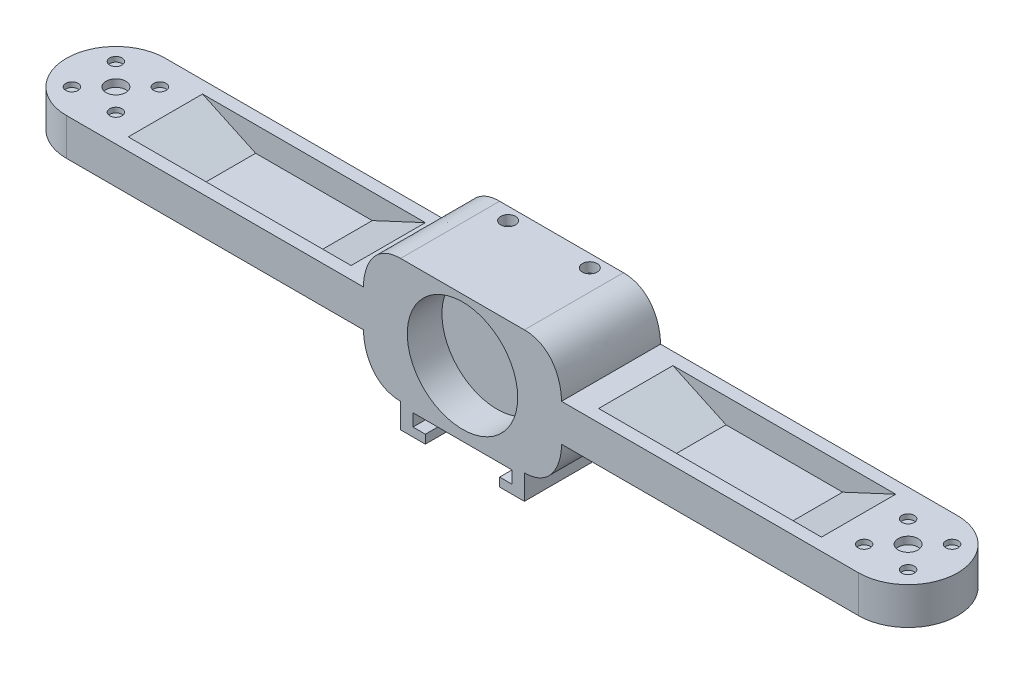
SolidWorks part; units mm, degrees
ref_plane "Front Plane" through (0, 0, 0) normal (0, 0, 1) x (1, 0, 0)
ref_plane "Top Plane" through (0, 0, 0) normal (0, 1, 0) x (1, 0, 0)
ref_plane "Right Plane" through (0, 0, 0) normal (1, 0, 0) x (0, 0, -1)
sketch "Sketch1" plane through (0, 0, 0) normal (0, 1, 0) x (1, 0, 0)
  line L0 (-80, 0) -> (80, 0) construction
  line L1 (-80, 10) -> (80, 10)
  line L2 (-80, -10) -> (80, -10)
  arc A0 (-80, 10) -> (-80, -10) centre (-80, 0) ccw
  arc A1 (80, -10) -> (80, 10) centre (80, 0) ccw
  point P2 (0, 0)
  dimension "D1" = 160
  dimension "D2" = 20
extrude "Boss-Extrude1" add sketch "Sketch1" along normal blind 25 contours L1 A1 L2 A0
sketch "Sketch2" plane through (0, 0, 10) normal (0, 0, 1) x (1, 0, 0)
  line L0 (0, 0) -> (0, 12.5) construction
  circle A0 centre (0, 12.5) radius 11.15
  dimension "D2" = 22.3
  dimension "D1" = 12.5
extrude "Cut-Extrude1" cut sketch "Sketch2" against normal blind 7 contours A0
sketch "Sketch3" plane through (0, 25, 0) normal (0, 1, 0) x (1, 0, 0)
  line L0 (0, 0) -> (20, 0) construction
  line L1 (0, 0) -> (-20, 0) construction
  line L2 (-20, 10) -> (-20, -10)
  line L3 (-80, 10) -> (80, 10) construction
  line L4 (-80, -10) -> (80, -10) construction
  line L5 (20, 10) -> (20, -10)
  line L6 (20, -10) -> (80, -10)
  line L7 (20, 10) -> (80, 10)
  line L8 (-20, 10) -> (-80, 10)
  line L9 (-20, -10) -> (-80, -10)
  arc A0 (-80, 10) -> (-80, -10) centre (-80, 0) ccw
  arc A1 (80, 10) -> (80, -10) centre (80, 0) cw
  dimension "D2" = 20
  dimension "D1" = 20
extrude "Cut-Extrude2" cut sketch "Sketch3" against normal blind 8.75
sketch "Sketch4" plane through (0, 0, 0) normal (0, -1, 0) x (1, 0, 0)
  line L2 (20, 10) -> (20, -10)
  line L3 (-80, 10) -> (80, 10) construction
  line L4 (20, -10) -> (80, -10)
  line L5 (20, 10) -> (80, 10)
  line L6 (-20, 10) -> (-20, -10)
  line L7 (-20, -10) -> (-80, -10)
  line L8 (-20, 10) -> (-80, 10)
  arc A0 (80, 10) -> (80, -10) centre (80, 0) cw
  arc A1 (-80, 10) -> (-80, -10) centre (-80, 0) ccw
extrude "Cut-Extrude3" cut sketch "Sketch4" against normal blind 8.75
sketch "Sketch5" plane through (0, 0, -10) normal (0, 0, -1) x (-1, 0, 0)
  line L0 (0, 0) -> (0, 12.5) construction
  line L2 (-12.5, 2.25) -> (12.5, 2.25)
  line L3 (-12.5, 2.25) -> (-12.5, 22.75)
  line L4 (-12.5, 22.75) -> (12.5, 22.75)
  line L5 (12.5, 2.25) -> (12.5, 22.75)
  line L6 (-12.5, 2.25) -> (12.5, 22.75) construction
  line L7 (-12.5, 22.75) -> (12.5, 2.25) construction
  dimension "D1" = 12.5
  dimension "D2" = 25
  dimension "D3" = 20.5
extrude "Cut-Extrude4" cut sketch "Sketch5" against normal blind 8
sketch "Sketch9" plane through (0, 16.25, 0) normal (0, 1, 0) x (1, 0, 0)
  line L0 (-80, 10) -> (-80, -10) construction
  line L1 (0, 0) -> (0, 5) construction
  circle A0 centre (-80, 0) radius 2
  circle A1 centre (80, 0) radius 2
  dimension "D1" = 4
  dimension "D2" = 5
extrude "Cut-Extrude5" cut sketch "Sketch9" against normal blind 1.5
sketch "Sketch10" plane through (0, 16.25, 0) normal (0, 1, 0) x (1, 0, 0)
  line L0 (-80, 0) -> (-80, 4.44) construction
  line L1 (-80, 4.44) -> (-75.56, 4.44) construction
  line L2 (0, 0) -> (0, 5) construction
  circle A0 centre (-75.56, 4.44) radius 1.25
  circle A1 centre (-75.56, -4.44) radius 1.25
  circle A2 centre (-84.44, -4.44) radius 1.25
  circle A3 centre (-84.44, 4.44) radius 1.25
  circle A4 centre (84.44, 4.44) radius 1.25
  circle A5 centre (84.44, -4.44) radius 1.25
  circle A6 centre (75.56, -4.44) radius 1.25
  circle A7 centre (75.56, 4.44) radius 1.25
  point P14 (-80, 0)
  dimension "D3" = 2.5
  dimension "D1" = 4.44
  dimension "D2" = 4.44
  dimension "D5" = 5
  dimension "D4" = 4
extrude "Cut-Extrude6" cut sketch "Sketch10" against normal blind 1
sketch "Sketch13" plane through (0, 8.75, 0) normal (0, -1, 0) x (1, 0, 0)
  line L0 (-80, 10) -> (-80, -10) construction
  line L1 (-80, 0) -> (-75.56, 0) construction
  line L2 (-75.56, 0) -> (-75.56, 4.44) construction
  line L3 (0, 0) -> (0, 5) construction
  circle A0 centre (-75.56, 4.44) radius 2.4
  circle A1 centre (-75.56, -4.44) radius 2.4
  circle A2 centre (-84.44, -4.44) radius 2.4
  circle A3 centre (-84.44, 4.44) radius 2.4
  circle A4 centre (84.44, 4.44) radius 2.4
  circle A5 centre (84.44, -4.44) radius 2.4
  circle A6 centre (75.56, -4.44) radius 2.4
  circle A7 centre (75.56, 4.44) radius 2.4
  point P18 (-80, 0)
  dimension "D1" = 4.44
  dimension "D2" = 4.44
  dimension "D5" = 5
  dimension "D4" = 4
  dimension "D3" = 4.8
extrude "Cut-Extrude7" cut sketch "Sketch13" against normal offset from surface (4.5 mm away) 3 up to face at (84.44, 16.25, -5.69)
sketch "Sketch14" plane through (0, 25, 0) normal (0, 1, 0) x (1, 0, 0)
  line L0 (0, 0) -> (0, 10) construction
  line L1 (-20, 10) -> (20, 10) construction
  line L2 (0, 10) -> (-8.25, 10) construction
  line L3 (-8.25, 10) -> (-8.25, 7.46) construction
  circle A0 centre (-8.25, 7.46) radius 1.5
  circle A1 centre (8.25, 7.46) radius 1.5
  dimension "D3" = 3
  dimension "D1" = 8.25
  dimension "D2" = 2.54
extrude "Cut-Extrude8" cut sketch "Sketch14" against normal blind 2
sketch "Sketch16" plane through (0, 0, -10) normal (0, 0, -1) x (-1, 0, 0)
  line L0 (0, 0) -> (0, 25) construction
  line L1 (20, 25) -> (-20, 25) construction
  line L2 (-12.5, 22.75) -> (-12.5, 25) construction
  line L3 (0, 12.5) -> (-20, 12.5) construction
  line L4 (-12.5, 25) -> (-20, 25)
  line L5 (-20, 25) -> (-20, 16.25)
  line L6 (12.5, 25) -> (20, 25)
  line L7 (20, 25) -> (20, 16.25)
  line L8 (20, 0) -> (20, 8.75)
  line L9 (12.5, 0) -> (20, 0)
  line L10 (-20, 0) -> (-20, 8.75)
  line L11 (-12.5, 0) -> (-20, 0)
  spline S0 degree 3 poles (-20, 16.25) (-20, 20.0915) (-17.8821, 25) (-12.5, 25) knots 0 0 0 0 1 1 1 1
  spline S1 degree 3 poles (20, 16.25) (20, 20.0915) (17.8821, 25) (12.5, 25) knots 0 0 0 0 1 1 1 1
  spline S2 degree 3 poles (20, 8.75) (20, 4.9085) (17.8821, 0) (12.5, 0) knots 0 0 0 0 1 1 1 1
  spline S3 degree 3 poles (-20, 8.75) (-20, 4.9085) (-17.8821, 0) (-12.5, 0) knots 0 0 0 0 1 1 1 1
  dimension "D2" = 20
extrude "Cut-Extrude10" cut sketch "Sketch16" against normal blind 20
sketch "Sketch17" plane through (0, 0, -10) normal (0, 0, -1) x (-1, 0, 0)
  line L0 (12.5, 0) -> (12.5, -5)
  line L1 (-12.5, 0) -> (12.5, 0)
  line L5 (12.5, -5) -> (7.5, -5)
  line L17 (7.5, -5) -> (7.5, -3.25)
  line L18 (7.5, -3.25) -> (10, -3.25)
  line L19 (10, -3.25) -> (10, -0.75)
  line L20 (10, -0.75) -> (-10, -0.75)
  line L21 (-10, -0.75) -> (-10, -3.25)
  line L22 (-10, -3.25) -> (-7.5, -3.25)
  line L23 (-7.5, -3.25) -> (-7.5, -5)
  line L24 (-7.5, -5) -> (-12.5, -5)
  line L25 (-12.5, -5) -> (-12.5, 0)
  dimension "D1" = 20
  dimension "D2" = 25
  dimension "D3" = 2.5
  dimension "D4" = 2.5
  dimension "D5" = 5
  dimension "D6" = 2.5
  dimension "D7" = 1.75
  dimension "D8" = 1.75
  dimension "D9" = 2.5
  dimension "D10" = 5
extrude "Boss-Extrude2" add sketch "Sketch17" against normal blind 20
sketch "Sketch18" plane through (0, 16.25, 0) normal (0, 1, 0) x (1, 0, 0)
  line L0 (0, 0) -> (-20, 0) construction
  line L1 (-20, -10) -> (-20, 10) construction
  line L2 (-90, 0) -> (-70, 0) construction
  line L3 (-20, 0) -> (-25, 0) construction
  line L4 (-70, 0) -> (-25, 0) construction
  line L5 (-20, 10) -> (-25, 10) construction
  line L6 (-20, 10) -> (-80, 10) construction
  line L7 (-25, 10) -> (-25, 7.5) construction
  line L8 (0, 0) -> (0, 10) construction
  line L9 (70, 7.5) -> (25, 7.5)
  line L10 (-70, -7.5) -> (-25, -7.5)
  line L11 (-70, -7.5) -> (-70, 7.5)
  line L12 (-70, 7.5) -> (-25, 7.5)
  line L13 (-25, -7.5) -> (-25, 7.5)
  line L14 (-70, -7.5) -> (-25, 7.5) construction
  line L15 (-70, 7.5) -> (-25, -7.5) construction
  line L16 (25, -7.5) -> (25, 7.5)
  line L17 (70, -7.5) -> (25, -7.5)
  line L18 (70, -7.5) -> (70, 7.5)
  line L19 (70, 7.5) -> (25, -7.5) construction
  line L20 (70, -7.5) -> (25, 7.5) construction
  arc A0 (-80, 10) -> (-80, -10) centre (-80, 0) ccw construction
  point P17 (-47.5, 0)
  point P27 (47.5, 0)
  dimension "D1" = 20
  dimension "D2" = 5
  dimension "D3" = 5
  dimension "D4" = 2.5
  dimension "D5" = 10
extrude "Cut-Extrude11" cut sketch "Sketch18" against normal blind 5
sketch "Sketch20" plane through (0, 0, 10) normal (0, 0, 1) x (1, 0, 0)
  line L0 (-25, 11.25) -> (-25, 16.25)
  line L4 (-25, 11.25) -> (-35.7225, 11.25)
  line L5 (-70, 11.25) -> (-25, 11.25) construction
  line L6 (-35.7225, 11.25) -> (-25, 16.25)
  line L7 (-47.5, 11.25) -> (-47.5, 16.25) construction
  line L8 (-80, 16.25) -> (-20, 16.25) construction
  line L9 (-70, 11.25) -> (-59.2775, 11.25)
  line L10 (-70, 11.25) -> (-70, 16.25)
  line L11 (-59.2775, 11.25) -> (-70, 16.25)
  line L12 (0, 0) -> (0, 25) construction
  line L13 (-12.5, 25) -> (12.5, 25) construction
  line L14 (25, 11.25) -> (35.7225, 11.25)
  line L15 (25, 11.25) -> (25, 16.25)
  line L16 (35.7225, 11.25) -> (25, 16.25)
  line L17 (70, 11.25) -> (70, 16.25)
  line L18 (59.2775, 11.25) -> (70, 16.25)
  line L19 (70, 11.25) -> (59.2775, 11.25)
  dimension "D1" = 65
extrude "Boss-Extrude3" add sketch "Sketch20" against normal blind 20
equation "\"Cent to Cent length\"= 16cm"
equation "\"D1@Sketch1\"=\"Cent to Cent length\""
equation "\"Width\"= 2cm"
equation "\"D2@Sketch1\"=\"Width\""
equation "\"XY for Motor Mounts\"= .444cm"
equation "\"Diam for large MM hole\"= .48cm"
equation "\"Diam for small MM hole\"= .25cm"
equation "\"D1@Sketch10\"=\"XY for Motor Mounts\""
equation "\"D2@Sketch10\"=\"XY for Motor Mounts\""
equation "\"D3@Sketch10\"=\"Diam for small MM hole\""
equation "\"D1@Sketch13\"=\"XY for Motor Mounts\""
equation "\"D2@Sketch13\"=\"XY for Motor Mounts\""
equation "\"D3@Sketch13\"=\"Diam for large MM hole\""
equation "\"Hole distance / 2 for Accelerometer\"= 8.25mm"
equation "\"Hole distance from edge for accelerometer\"= 2.54mm"
equation "\"D1@Sketch14\"=\"Hole distance / 2 for Accelerometer\""
equation "\"D2@Sketch14\"=\"Hole distance from edge for accelerometer\""
equation "\"Center Housing Width/2\"= 2cm"
equation "\"D1@Sketch3\"=\"Center Housing Width/2\""
equation "\"D2@Sketch3\"=\"Center Housing Width/2\""
equation "\"D2@Sketch16\"=\"Center Housing Width/2\""
equation "\"D1@Cut-Extrude10\"=\"Width\""
equation "\"D1@Boss-Extrude2\"=\"Width\""
equation "\"D1@Boss-Extrude3\"=\"Width\""
equation "\"Draft Angle, ESC Recess\"= 65deg"
equation "\"D1@Sketch20\"=\"Draft Angle, ESC Recess\""
equation "\"Screw Depth for Motors\"= .3cm"
equation "\"D1@Cut-Extrude7\"=\"Screw Depth for Motors\""
